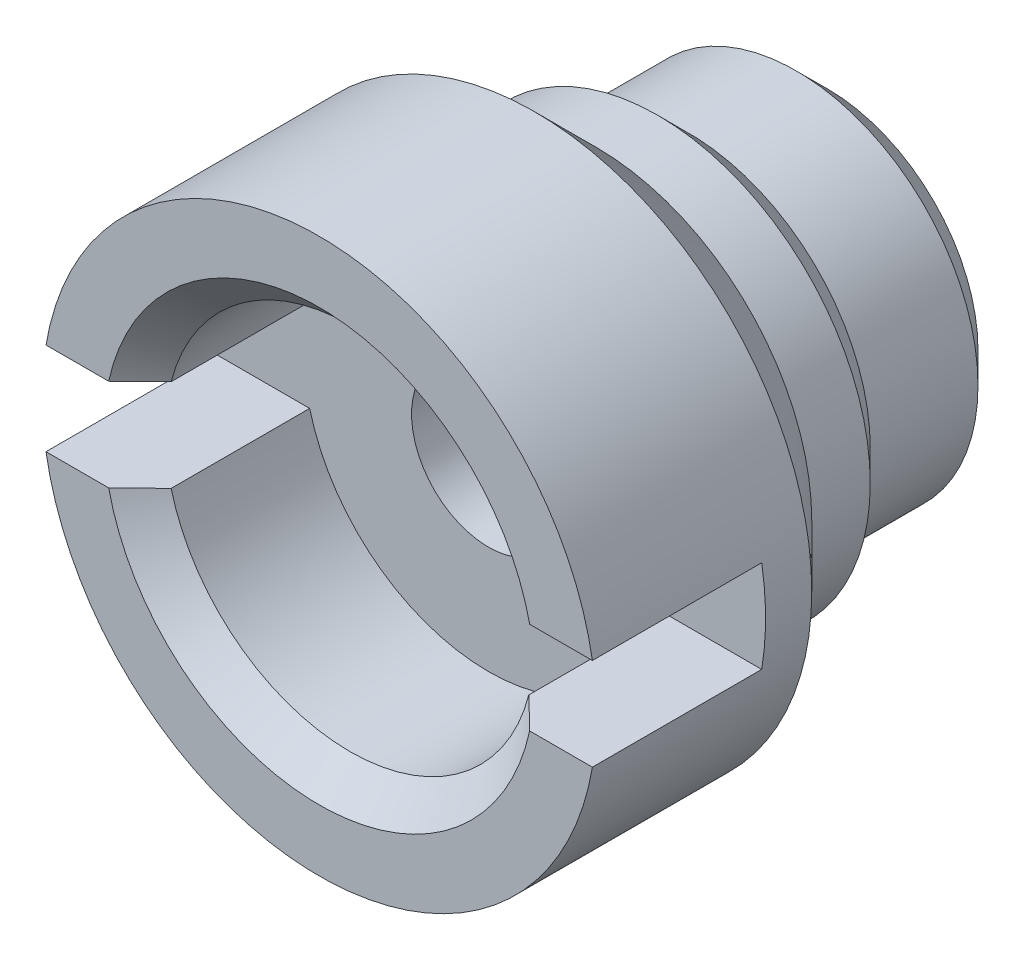
SolidWorks part; units mm, degrees
ref_plane "Front Plane" through (0, 0, 0) normal (0, 0, 1) x (1, 0, 0)
ref_plane "Top Plane" through (0, 0, 0) normal (0, 1, 0) x (1, 0, 0)
ref_plane "Right Plane" through (0, 0, 0) normal (1, 0, 0) x (0, 0, -1)
sketch "Sketch1" plane through (0, 0, 0) normal (0, 0, 1) x (1, 0, 0)
  circle A0 centre (0, 0) radius 2.95
  circle A1 centre (0, 0) radius 1.25
  dimension "D1" = 5.9
  dimension "D2" = 2.5
extrude "Boss-Extrude1" add sketch "Sketch1" along normal blind 3.75
sketch "Sketch2" plane through (0, 0, 3.75) normal (0, 0, 1) x (1, 0, 0)
  circle A0 centre (0, 0) radius 1.25
  circle A1 centre (0, 0) radius 4.5
  circle A2 centre (0, 0) radius 1.25 construction
  dimension "D1" = 9
extrude "Boss-Extrude2" add sketch "Sketch2" along normal blind 4.5
sketch "Sketch3" plane through (0, 0, 8.25) normal (0, 0, 1) x (1, 0, 0)
  circle A0 centre (0, 0) radius 3
  dimension "D1" = 6
extrude "Cut-Extrude1" cut sketch "Sketch3" against normal blind 2.75
chamfer "Chamfer1" distance 0.5 angle 45 1 edges at (3, 0, 8.25)
chamfer "Chamfer2" distance 0.5 angle 45 1 edges at (2.95, 0, 0)
sketch "Sketch4" plane through (0, 0, 3.75) normal (0, 0, -1) x (-1, 0, 0)
  circle A0 centre (0, 0) radius 1.25
  circle A1 centre (0, 0) radius 3.45
  circle A2 centre (0, 0) radius 1.25 construction
  circle A3 centre (0, 0) radius 2.95 construction
  dimension "D1" = 0.5
extrude "Boss-Extrude3" add sketch "Sketch4" along normal blind 1.5
chamfer "Chamfer3" distance 1 angle 45 1 edges at (4.5, 0, 3.75)
chamfer "Chamfer6" distance 0.5 angle 45 1 edges at (-3.45, 0, 2.25)
sketch "Sketch5" plane through (0, 0, 8.25) normal (0, 0, 1) x (1, 0, 0)
  line L1 (6.0839, 0.75) -> (-6.0839, 0.75)
  line L2 (6.0839, 0.75) -> (6.0839, -0.75)
  line L3 (6.0839, -0.75) -> (-6.0839, -0.75)
  line L4 (-6.0839, 0.75) -> (-6.0839, -0.75)
  line L5 (6.0839, 0.75) -> (-6.0839, -0.75) construction
  line L6 (6.0839, -0.75) -> (-6.0839, 0.75) construction
  point P0 (0, 0)
  dimension "D1" = 1.5
extrude "Cut-Extrude2" cut sketch "Sketch5" against normal up to surface (2.75 mm away) up to face at (1.25, 0, 5.5)
